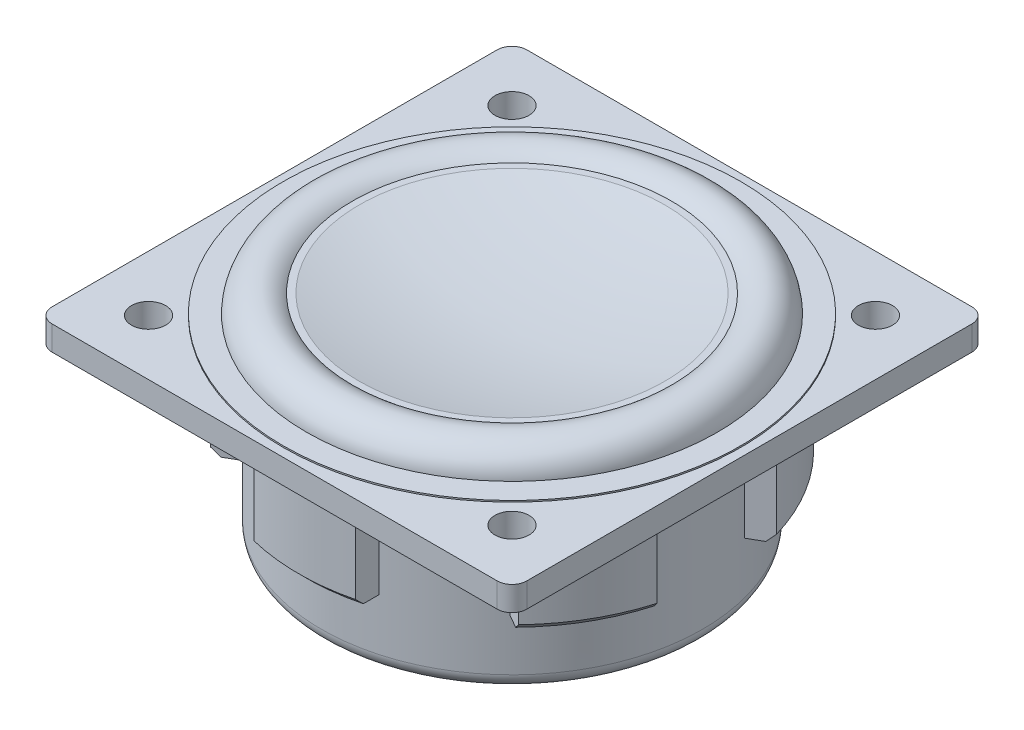
SolidWorks part; units mm, degrees
material "ABS"
ref_plane "Front" through (0, 0, 0) normal (0, 0, 1) x (1, 0, 0)
ref_plane "Top" through (0, 0, 0) normal (0, 1, 0) x (1, 0, 0)
ref_plane "Right" through (0, 0, 0) normal (1, 0, 0) x (0, 0, -1)
sketch "Эскиз1" plane through (0, 0, 0) normal (0, 1, 0) x (1, 0, 0)
  line L0 (16, -16) -> (16, 16)
  line L1 (16, -16) -> (-16, -16)
  line L2 (16, 16) -> (-16, 16)
  line L3 (-16, -16) -> (-16, 16)
  line L4 (16, -16) -> (-16, 16) construction
  line L5 (16, 16) -> (-16, -16) construction
  point P1 (0, 0)
  dimension "D1" = 32
  dimension "D2" = 32
extrude "Бобышка-Вытянуть1" add sketch "Эскиз1" against normal blind 1.65
sketch "Эскиз2" plane through (0, 0, 0) normal (1, 0, 0) x (0, 0, -1)
  line L0 (0, 0) -> (-15.425, 0)
  line L1 (-16, 0) -> (16, 0) construction
  line L2 (-15.425, 0) -> (-15.425, 0.1)
  line L3 (-15.425, 0.1) -> (-13.85, 0.1)
  line L4 (-13.85, 0.1) -> (-13.85, 1.8)
  line L5 (-13.85, 1.8) -> (-10.75, 1.8)
  line L6 (-10.75, 1.8) -> (-10.75, 1.3)
  line L7 (-10.75, 1.3) -> (-10.3, 1.3)
  line L8 (0, 0) -> (0, -5.2055) construction
  line L9 (10.75, 1.3) -> (10.3, 1.3)
  line L10 (10.75, 1.8) -> (10.75, 1.3)
  line L11 (13.85, 1.8) -> (10.75, 1.8)
  line L12 (13.85, 0.1) -> (13.85, 1.8)
  line L13 (15.425, 0.1) -> (13.85, 0.1)
  line L14 (15.425, 0) -> (15.425, 0.1)
  line L15 (0, 0) -> (0, -1.65)
  line L16 (-16, -1.65) -> (16, -1.65) construction
  line L17 (0, -1.65) -> (-15.425, -1.65)
  line L18 (-15.425, -1.65) -> (-15.425, 0)
  arc A0 (-13.85, 0.1) -> (-10.75, 1.3) centre (-12.0123, -0.0433) cw
  arc A1 (13.85, 0.1) -> (10.75, 1.3) centre (12.0123, -0.0433) ccw
  arc A2 (-10.3, 1.3) -> (10.3, 1.3) centre (0, 41.4538) ccw
  dimension "D1" = 0.1
  dimension "D2" = 1.8
  dimension "D3" = 13.85
  dimension "D4" = 15.425
  dimension "D5" = 10.75
  dimension "D6" = 0.45
  dimension "D7" = 0.5
revolve "Повернуть2" add sketch "Эскиз2" angle 360 about L8 region at (0, -0.825, 7.7125) region at (0, 0.5899, 10.1154)
sketch "Эскиз3" plane through (0, -1.65, 0) normal (0, -1, 0) x (1, 0, 0)
  line L0 (3.425, -28.823) -> (3.425, 28.823)
  line L1 (3.425, -28.823) -> (-3.425, -28.823)
  line L2 (3.425, 28.823) -> (-3.425, 28.823)
  line L3 (-3.425, -28.823) -> (-3.425, 28.823)
  line L4 (3.425, -28.823) -> (-3.425, 28.823) construction
  line L5 (3.425, 28.823) -> (-3.425, -28.823) construction
  circle A0 centre (0, 0) radius 12.85
  circle A1 centre (0, 0) radius 14.375
  dimension "D1" = 28.75
  dimension "D2" = 25.7
  dimension "D3" = 6.85
extrude "Бобышка-Вытянуть2" add sketch "Эскиз3" along normal blind 11.25 contours A0
extrude "Бобышка-Вытянуть3" add sketch "Эскиз3<3>" along normal blind 6.75 contours L0 A1 L3 A0 | L3 A1 L0 A0 region at (0, -1.65, -13.4657) region at (0, -1.65, 13.4657)
sketch "Эскиз3<3>" plane through (0, -1.65, 0) normal (0, -1, 0) x (1, 0, 0) same geometry as "Эскиз3"
pattern_circular "Круговой массив1" count 6 over 360 about axis through (0, -12.9, 0) along (0, 1, 0) of "Бобышка-Вытянуть3" reverse direction yes
fillet "Скругление1" radius 1 4 edges at (16, -0.825, 16) (16, -0.825, -16) (-16, -0.825, -16) (-16, -0.825, 16)
fillet "Скругление2" radius 1 1 edges at (0, -12.9, -12.85)
sketch "Эскиз4" plane through (0, 0, 0) normal (0, 1, 0) x (1, 0, 0)
  line L0 (12.25, -12.25) -> (12.25, 12.25) construction
  line L1 (12.25, -12.25) -> (-12.25, -12.25) construction
  line L2 (12.25, 12.25) -> (-12.25, 12.25) construction
  line L3 (-12.25, -12.25) -> (-12.25, 12.25) construction
  line L4 (12.25, -12.25) -> (-12.25, 12.25) construction
  line L5 (12.25, 12.25) -> (-12.25, -12.25) construction
  circle A0 centre (-12.25, 12.25) radius 1.15
  circle A1 centre (12.25, 12.25) radius 1.15
  circle A2 centre (12.25, -12.25) radius 1.15
  circle A3 centre (-12.25, -12.25) radius 1.15
  point P1 (0, 0)
  dimension "D3" = 2.3
  dimension "D4" = 2.3
  dimension "D5" = 2.3
  dimension "D6" = 2.3
  dimension "D1" = 24.5
  dimension "D2" = 24.5
extrude "Вырез-Вытянуть2" cut sketch "Эскиз4" against normal through all
chamfer "Фаска1" distance 0.5 angle 45 6 edges at (0, -8.4, -14.375) (12.4491, -8.4, -7.1875) (12.4491, -8.4, 7.1875) (0, -8.4, 14.375) (-12.4491, -8.4, 7.1875) (-12.4491, -8.4, -7.1875)
